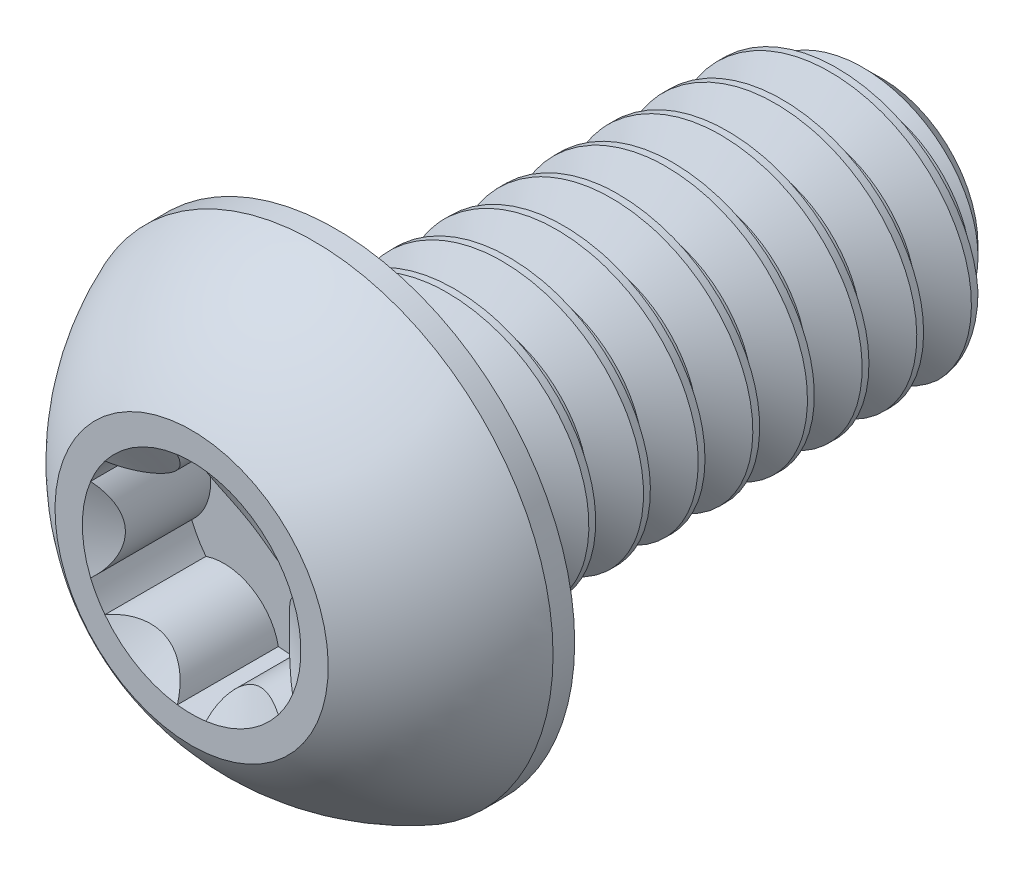
SolidWorks part; units mm, degrees
material "Plain Carbon Steel"
ref_plane "Front" through (0, 0, 0) normal (0, 0, 1) x (1, 0, 0)
ref_plane "Top" through (0, 0, 0) normal (0, 1, 0) x (1, 0, 0)
ref_plane "Right" through (0, 0, 0) normal (1, 0, 0) x (0, 0, -1)
sketch "Sketch1" plane through (0, 0, 0) normal (1, 0, 0) x (0, 0, -1)
  line L2 (3.3528, 3.175) -> (16.0528, 3.175)
  line L3 (16.0528, 3.175) -> (16.0528, 0)
  line L4 (16.0528, 0) -> (3.3528, 0)
  line L6 (2.8499, 5.5499) -> (3.3528, 5.5499) construction
  line L7 (16.0528, 3.175) -> (16.0528, -3.175) construction
  line L8 (0, 0) -> (3.3528, 0) construction
  line L9 (3.3528, 5.5499) -> (3.3528, -5.5499) construction
  line L11 (3.3528, 3.175) -> (3.3528, 0)
  line L14 (0, 0) -> (0, 3.175) construction
  arc A3 (0, 3.175) -> (2.8499, 5.5499) centre (5.0603, 0) cw construction
  dimension "D1" = 0.5029
revolve "Revolve1" add sketch "Sketch1" angle 360 mid plane about L4
sketch "Sketch3" plane through (0, 0, -16.0528) normal (0, 0, -1) x (-1, 0, 0)
  circle A0 centre (0, 0) radius 3.175
curve "Helix/Spiral1" pitch 1.27 height 13.97 radius 3.175 centre (0, 0, -16.0528) axis (0, 0, 1) start towards (0, 1, 0)
sketch "Sketch2" plane through (0, 0, 0) normal (1, 0, 0) x (0, 0, -1)
  line L0 (16.0528, 3.175) -> (17.164, 3.175)
  line L1 (17.164, 3.175) -> (16.6878, 2.3501)
  line L2 (16.6878, 2.3501) -> (16.529, 2.3501)
  line L3 (16.529, 2.3501) -> (16.0528, 3.175)
  line L4 (16.2909, 2.7626) -> (16.9259, 2.7626) construction
  dimension "D1" = 60
  dimension "D2" = 0.1588
  dimension "D3" = 0.635
chamfer "Chamfer1" distance 0.9525 angle 45 1 edges at (0, 3.175, -16.0528)
sweep "Cut-Sweep1" cut profiles "Sketch2" path "Helix/Spiral1" align with end faces yes
sketch "Sketch7" plane through (0, 0, 0) normal (1, 0, 0) x (0, 0, -1)
  line L0 (0, 0) -> (0, 3.175) construction
  line L6 (2.8499, 5.5499) -> (3.3528, 5.5499) construction
  line L8 (0, 0) -> (3.3528, 0) construction
  line L11 (3.3528, 5.5499) -> (3.3528, -5.5499) construction
  line L12 (2.8499, 5.5499) -> (3.3528, 5.5499)
  line L13 (0, 0) -> (3.3528, 0)
  line L15 (3.3528, 5.5499) -> (3.3528, 0)
  line L16 (0, 3.175) -> (0, 0)
  arc A2 (2.8499, 5.5499) -> (0, 3.175) centre (5.0603, 0) ccw construction
  arc A3 (2.8499, 5.5499) -> (0, 3.175) centre (5.0603, 0) ccw
revolve "Revolve2" add sketch "Sketch7" angle 360 mid plane about L13
sketch "Sketch5" plane through (0, 0, 0) normal (0, 0, 1) x (1, 0, 0)
  line L1 (0, 0) -> (-2.54, 0) construction
  line L2 (0, 0) -> (-2.1997, 1.27) construction
  line L3 (0, 0) -> (-2.1997, -1.27) construction
  line L4 (-2.1997, -1.27) -> (0, 0)
  line L5 (0, 0) -> (-2.1997, 1.27)
  line L6 (0, 0) -> (-2.3467, -0.972) construction
  line L7 (0, 2.54) -> (0, 2.2225) construction
  line L8 (0, 2.2225) -> (0, 1.905) construction
  circle A0 centre (0, 0) radius 2.54 construction
  circle A3 centre (0, 0) radius 2.2225 construction
  circle A4 centre (0, 0) radius 1.905 construction
  arc A5 (-2.3467, -0.972) -> (-2.3467, 0.972) centre (-3.1955, 0) ccw
  arc A6 (-2.3467, 0.972) -> (-2.1997, 1.27) centre (0, 0) cw
  arc A7 (-2.3467, -0.972) -> (-2.1997, -1.27) centre (0, 0) ccw
  dimension "D5" = 3.81
  dimension "D1" = 30
  dimension "D3" = 7.5
extrude "Cut-Extrude2" cut sketch "Sketch5" against normal blind 2.347
pattern_circular "CirPattern1" count 6 over 360 about axis through (0, 0, 0) along (0, 0, 1) of "Cut-Extrude2"
sketch "Sketch11" plane through (0, 0, 0) normal (0, 0, 1) x (1, 0, 0)
  circle A1 centre (0, 0) radius 2.54 construction
  circle A2 centre (0, 0) radius 2.54
extrude "Cut-Extrude3" cut sketch "Sketch11" against normal blind 2.347 draft 60
sketch "Sketch9" [suppressed] plane through (0, 0, -5.0292) normal (0, 0, 1) x (1, 0, 0)
  circle A2 centre (0, 0) radius 4.7625
extrude "Boss-Extrude2" [suppressed] add sketch "Sketch9" against normal offset from surface (6.35 mm away) 31.75
sketch "Sketch10" plane through (0, 0, 0) normal (1, 0, 0) x (0, 0, -1)
  line L0 (16.0528, 3.175) -> (16.0528, -3.175) construction
  point P0 (14.1478, -3.175)
  dimension "D1" = 1.905
equation "\"D3@Helix/Spiral1\" = \"Lg@Sketch1\" + \"D4@Helix/Spiral1\""
equation "\"D2@Sketch2\" = \"D4@Helix/Spiral1\" * .125"
equation "\"D3@Sketch2\" = \"D4@Helix/Spiral1\" * .5"
equation "\"D1@Chamfer1\" = \"D4@Helix/Spiral1\" * .75"
equation "\"D1@Cut-Extrude2\" = \"Head Ht@Sketch1\" * .7"
equation "\"D1@Sketch1\" = \"Head Ht@Sketch1\" * .15"
equation "\"D1@Sketch10\" = \"D4@Helix/Spiral1\" * 1.5"
equation "\"D1@Cut-Extrude3\" = \"D1@Cut-Extrude2\""
equation "\"D4@Sketch5\" = \"Dia@Sketch1\" * .8"
equation "\"D5@Sketch5\" = \"D4@Sketch5\" * .75"
